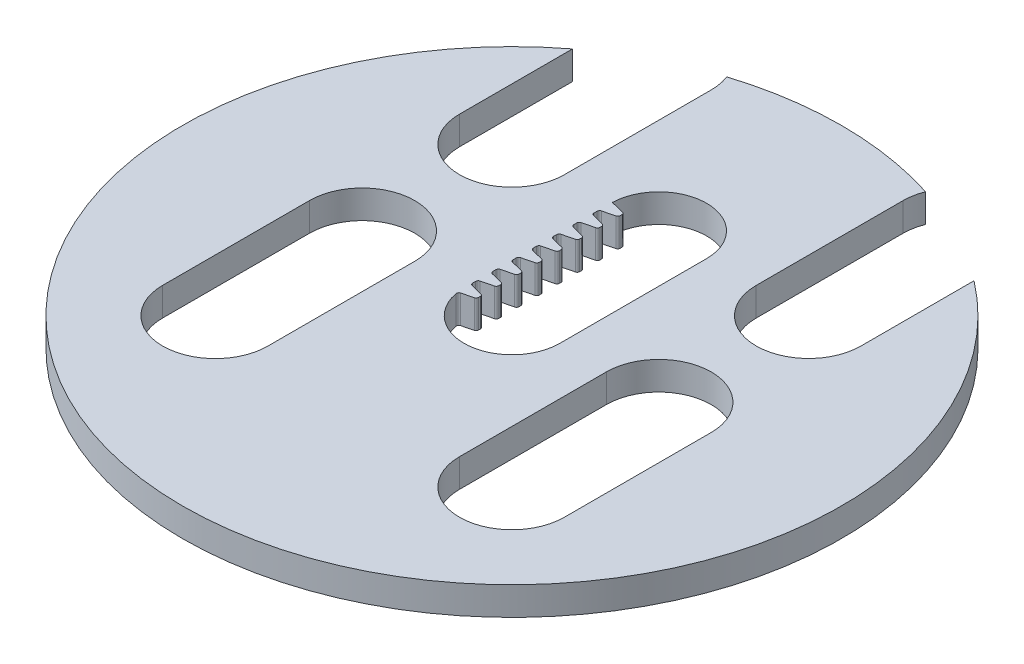
SolidWorks part; units mm, degrees
ref_plane "Front Plane" through (0, 0, 0) normal (0, 0, 1) x (1, 0, 0)
ref_plane "Top Plane" through (0, 0, 0) normal (0, 1, 0) x (1, 0, 0)
ref_plane "Right Plane" through (0, 0, 0) normal (1, 0, 0) x (0, 0, -1)
sketch "Sketch3" plane through (0, 0, 0) normal (0, -1, 0) x (1, 0, 0)
  line L0 (0, 0) -> (0, -17.78) construction
  line L1 (5.8, 0) -> (5.8, -17.78)
  line L2 (-5.8, 0) -> (-5.8, -17.78)
  line L3 (-17.9605, -35.7405) -> (17.9605, 0.1805) construction
  line L4 (-17.9605, 0.1805) -> (17.9605, -35.7405) construction
  line L5 (-17.9605, 0.1805) -> (17.9605, 0.1805) construction
  line L6 (-17.9605, 0.1805) -> (-17.9605, 17.9605) construction
  line L7 (-24.3305, 0.1805) -> (-24.3305, 17.9605)
  line L8 (-11.5905, 0.1805) -> (-11.5905, 17.9605)
  line L9 (-17.9605, -35.7405) -> (-17.9605, -17.9605) construction
  line L10 (-24.3105, -35.7405) -> (-24.3105, -17.9605)
  line L11 (-11.6105, -35.7405) -> (-11.6105, -17.9605)
  line L12 (17.9605, 0.1805) -> (17.9605, 17.9605) construction
  line L13 (11.6105, 0.1805) -> (11.6105, 17.9605)
  line L14 (24.3105, 0.1805) -> (24.3105, 17.9605)
  line L15 (17.9605, -35.7405) -> (17.9605, -17.9605) construction
  line L16 (11.6105, -35.7405) -> (11.6105, -17.9605)
  line L17 (24.3105, -35.7405) -> (24.3105, -17.9605)
  circle A0 centre (0, 0) radius 39.9034
  arc A1 (5.8, 0) -> (-5.8, 0) centre (0, 0) ccw
  arc A2 (-5.8, -17.78) -> (5.8, -17.78) centre (0, -17.78) ccw
  arc A3 (-24.3305, 0.1805) -> (-11.5905, 0.1805) centre (-17.9605, 0.1805) ccw
  arc A4 (-11.5905, 17.9605) -> (-24.3305, 17.9605) centre (-17.9605, 17.9605) ccw
  arc A5 (-24.3105, -35.7405) -> (-11.6105, -35.7405) centre (-17.9605, -35.7405) ccw
  arc A6 (-11.6105, -17.9605) -> (-24.3105, -17.9605) centre (-17.9605, -17.9605) ccw
  arc A7 (11.6105, 0.1805) -> (24.3105, 0.1805) centre (17.9605, 0.1805) ccw
  arc A8 (24.3105, 17.9605) -> (11.6105, 17.9605) centre (17.9605, 17.9605) ccw
  arc A9 (11.6105, -35.7405) -> (24.3105, -35.7405) centre (17.9605, -35.7405) ccw
  arc A10 (24.3105, -17.9605) -> (11.6105, -17.9605) centre (17.9605, -17.9605) ccw
  point P5 (0, -8.89)
  point P10 (-17.9605, 9.0705)
  point P13 (0, -17.78)
  point P16 (0, -17.78)
  point P22 (-17.9605, -26.8505)
  point P28 (17.9605, 9.0705)
  point P34 (17.9605, -26.8505)
  dimension "D1" = 79.8068
  dimension "D3" = 5.8
  dimension "D8" = 6.37
  dimension "D10" = 6.35
  dimension "D13" = 6.35
  dimension "D14" = 6.35
  dimension "D2" = 17.78
  dimension "D4" = 45
  dimension "D5" = 45
  dimension "D6" = 50.8
extrude "Boss-Extrude1" add sketch "Sketch3" along normal blind 3.175 and the other way blind 0.254 contours L17 A10 L16 A0 L11 A6 L10 L2 A2 L1 A1 L8 A4 L7 A3 L14 A8 L13 A7 region at (-17.1393, 0, 34.7811)
sketch "Sketch4" plane through (0, 0.254, 0) normal (0, 1, 0) x (1, 0, 0)
  line L0 (-5.8, 0) -> (-3.94, 0) construction
  line L1 (-3.94, -0.34) -> (-3.94, 0.34)
  line L2 (-3.94, 0.34) -> (-5.8, 0.8038)
  line L3 (-5.8, 0) -> (-5.8, 17.78) construction
  line L8 (-5.8, 0.8038) -> (-5.8, -0.8038)
  line L9 (-5.8, -0.8038) -> (-3.94, -0.34)
  point P7 (-3.94, 0)
  line M5 (-5.8, 0) -> (-5.8, 17.78)
  arc M8 (5.8, 0) -> (-5.8, 0) centre (0, 0) cw
  dimension "D3" = 76
  dimension "D1" = 1.86
  dimension "D2" = 0.34
extrude "Boss-Extrude2" add sketch "Sketch4" against normal up to surface (3.429 mm away) contours L1 L2 M5 M8 | L0 L9 L1 M8 | L8 L9 M8 region at (-4.9957, 0.254, -0.3016) region at (-5.7837, 0.254, 0.5979) region at (-4.9847, 0.254, 0.2975) up to face at (0, -3.175, -8.89)
pattern_linear "LPattern1" count 8 spacing 2.45 along (0, 0, -1) of "Boss-Extrude2"
fillet "Fillet1" radius 0.3 31 edges at (-3.94, -1.4605, 0.34) (-5.8, -1.4605, -1.6462) (-3.94, -1.4605, -2.11) (-3.94, -1.4605, -2.79) (-5.8, -1.4605, -3.2538) (-5.8, -1.4605, -4.0962) (-3.94, -1.4605, -4.56) (-3.94, -1.4605, -5.24) (-5.8, -1.4605, -5.7038) (-5.8, -1.4605, -6.5462) (-3.94, -1.4605, -7.01) (-3.94, -1.4605, -7.69) (-5.8, -1.4605, -8.1538) (-5.8, -1.4605, -8.9962) (-3.94, -1.4605, -9.46) (-3.94, -1.4605, -10.14) (-5.8, -1.4605, -10.6038) (-5.8, -1.4605, -11.4462) (-3.94, -1.4605, -11.91) (-3.94, -1.4605, -12.59) (-5.8, -1.4605, -13.0538) (-5.8, -1.4605, -13.8962) (-3.94, -1.4605, -14.36) (-3.94, -1.4605, -15.04) (-5.8, -1.4605, -15.5038) (-5.8, -1.4605, -16.3462) (-3.94, -1.4605, -16.81) (-3.94, -1.4605, -17.49) (-5.7459, -1.4605, 0.7903) (-5.8, -1.4605, -0.8038) (-3.94, -1.4605, -0.34)
equation "\"AIRFRAME_OD\"= 3.142in"
equation "\"AIRFRAME_ID\"= 3.00in"
equation "\"FLAT_T\"= 0.125in"
equation "\"COUPLER_OD\"= 2.998in"
equation "\"COUPLER_ID\"= 2.875in"
equation "\"NOSE_EXP_L\"= 3.5in"
equation "\"NOSE_SHOULDER_L\"= 5in"
equation "\"MAIN_L\"= 30in"
equation "\"RECO_COUP_L\"= 6in"
equation "\"RECO_SWITCH_L\"= 1.5in"
equation "\"RECO_ROD_X\"= 1.5in"
equation "\"DROGUE_L\"= 14in"
equation "\"ATS_FORE_COUP_L\"= 4in"
equation "\"ATS_AFT_COUP_L\"= 2.5in"
equation "\"ATS_ROD_X\"= 2in"
equation "\"LOWER_L\"= 16in"
equation "\"FIN_ROOT\"= 5in"
equation "\"FIN_X\"= 0.75in"
equation "\"FIN_N\"= 4"
equation "\"MOTOR_OD\"= 2.25in"
equation "\"MOTOR_ID\"= 2.126in"
equation "\"MOTOR_L\"= 8in"
equation "\"MOTOR_LOWER_X\"= 0.5in"
equation "\"CR_AFT_X\"= 0.5in"
equation "\"CR_FORE_X\"= 6in"
equation "\"D1@Boss-Extrude1\"=\"FLAT_T\""
equation "\"D1@Sketch3\"=\"AIRFRAME_OD\""
equation "\"D6@Sketch3\"=\"ATS_ROD_X\""
